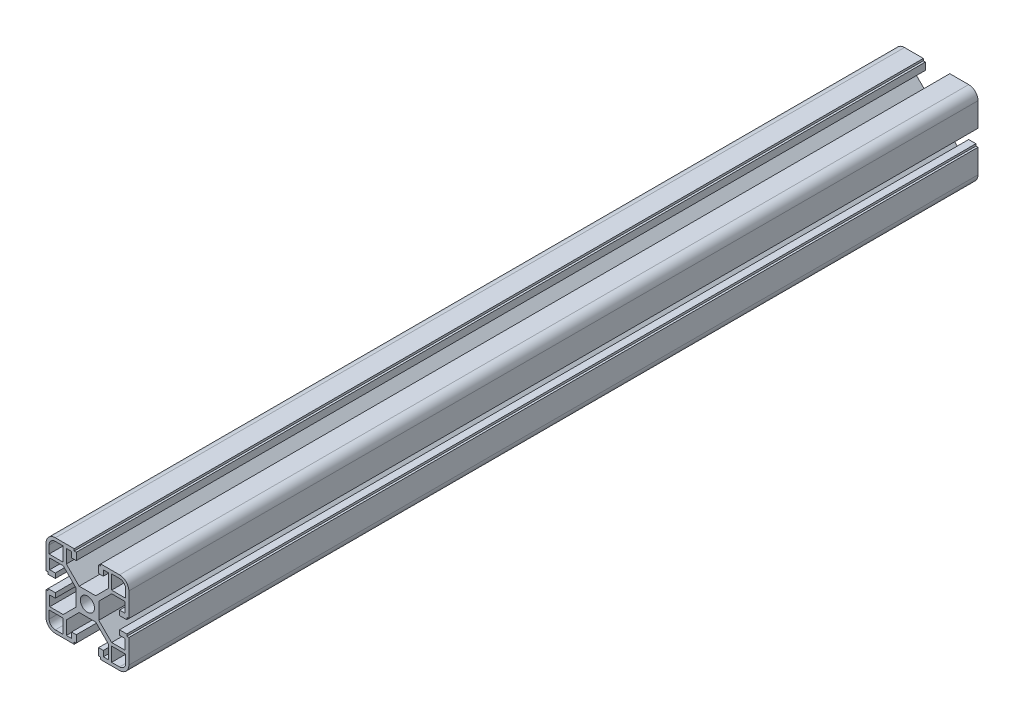
SolidWorks part; units mm, degrees
material "6061-T6 (SS)"
ref_plane "Front Plane" through (0, 0, 0) normal (0, 0, 1) x (1, 0, 0)
ref_plane "Top Plane" through (0, 0, 0) normal (0, 1, 0) x (1, 0, 0)
ref_plane "Right Plane" through (0, 0, 0) normal (1, 0, 0) x (0, 0, -1)
sketch "Sketch1" plane through (0, 0, 0) normal (0, 0, 1) x (1, 0, 0)
  line L0 (3.4, 0) -> (5.5, 0)
  line L1 (10.19, 11.69) -> (4, 5.5)
  line L2 (11.69, 10.19) -> (5.5, 4)
  line L3 (18.2, 10.19) -> (11.69, 10.19)
  line L4 (18.2, 10.19) -> (18.2, 5.2656)
  line L5 (18.2, 5.2656) -> (15.5, 5.2656)
  line L6 (15.5, 5.2656) -> (15.5, 2.9656)
  line L7 (15.5, 2.9656) -> (19, 2.9656)
  line L8 (19, 2.9656) -> (19, 3.9656)
  line L9 (19, 3.9656) -> (20, 3.9656)
  line L10 (20, 3.9656) -> (20, 15.5)
  line L11 (15.5, 20) -> (6.3853, 20)
  line L12 (18.5, 11.69) -> (18.5, 15.5)
  line L13 (15.5, 18.5) -> (11.69, 18.5)
  line L14 (11.69, 11.69) -> (11.69, 18.5)
  line L15 (0, 3.4) -> (0, 5.5)
  line L16 (4, 5.5) -> (0, 5.5)
  line L17 (6.3853, 20) -> (6.3853, 19)
  line L18 (5.5, 0) -> (5.5, 4)
  line L19 (6.3853, 19) -> (5.3853, 19)
  line L20 (5.3853, 19) -> (5.3853, 15.5)
  line L21 (5.3853, 15.5) -> (7.6853, 15.5)
  line L22 (10.19, 11.69) -> (10.19, 18.2)
  line L23 (11.69, 11.69) -> (18.5, 11.69)
  line L24 (7.6853, 18.2) -> (7.6853, 15.5)
  line L25 (10.19, 18.2) -> (7.6853, 18.2)
  arc A0 (20, 15.5) -> (15.5, 20) centre (15.5, 15.5) ccw
  arc A1 (18.5, 15.5) -> (15.5, 18.5) centre (15.5, 15.5) ccw
  arc A2 (3.4, 0) -> (0, 3.4) centre (0, 0) ccw
  dimension "D3" = 4.5
  dimension "D18" = 1.5
  dimension "D9" = 3.4
  dimension "D20" = 1.8
  dimension "D25" = 3
  dimension "D1" = 5.5
  dimension "D2" = 1.5
  dimension "D4" = 14.5
  dimension "D5" = 1.5
  dimension "D6" = 2.1
  dimension "D7" = 2.3
  dimension "D8" = 1.8
  dimension "D10" = 6.81
  dimension "D11" = 2.1
  dimension "D12" = 1
  dimension "D13" = 4.5
  dimension "D14" = 45
  dimension "D15" = 14.5
  dimension "D16" = 1
  dimension "D17" = 1.5
  dimension "D19" = 6.81
  dimension "D21" = 4.5
  dimension "D22" = 2.3
  dimension "D23" = 1
  dimension "D24" = 1
  dimension "D26" = 8.754
  dimension "D27" = 8.754
  dimension "D28" = 4.9244
  dimension "D29" = 2.5047
extrude "Boss-Extrude1" add sketch "Sketch1" along normal blind 410
mirror "Mirror1" about plane through (0, 0, 0) normal (0, 1, 0) of "Boss-Extrude1"
mirror "Mirror2" about plane through (0, 0, 0) normal (1, 0, 0) of "Boss-Extrude1"
mirror "Mirror3" about plane through (0, 0, 0) normal (0, 1, 0) of "Mirror2"
sketch "Croquis2" plane through (0, 0, 410) normal (0, 0, 1) x (1, 0, 0)
  line L0 (4, 5.5) -> (5.5, 4)
  line L1 (5.5, 4) -> (5.5, -4)
  line L2 (5.5, -4) -> (4, -5.5)
  line L3 (4, -5.5) -> (4, -23.2335)
  line L4 (4, -23.2335) -> (29.7306, -23.2335)
  line L5 (29.7306, -23.2335) -> (29.7306, 32.1268)
  line L6 (29.7306, 32.1268) -> (4, 32.1268)
  line L7 (4, 32.1268) -> (4, 5.5)
extrude "Cortar-Extruir2" [suppressed] cut sketch "Croquis2" against normal blind 70
